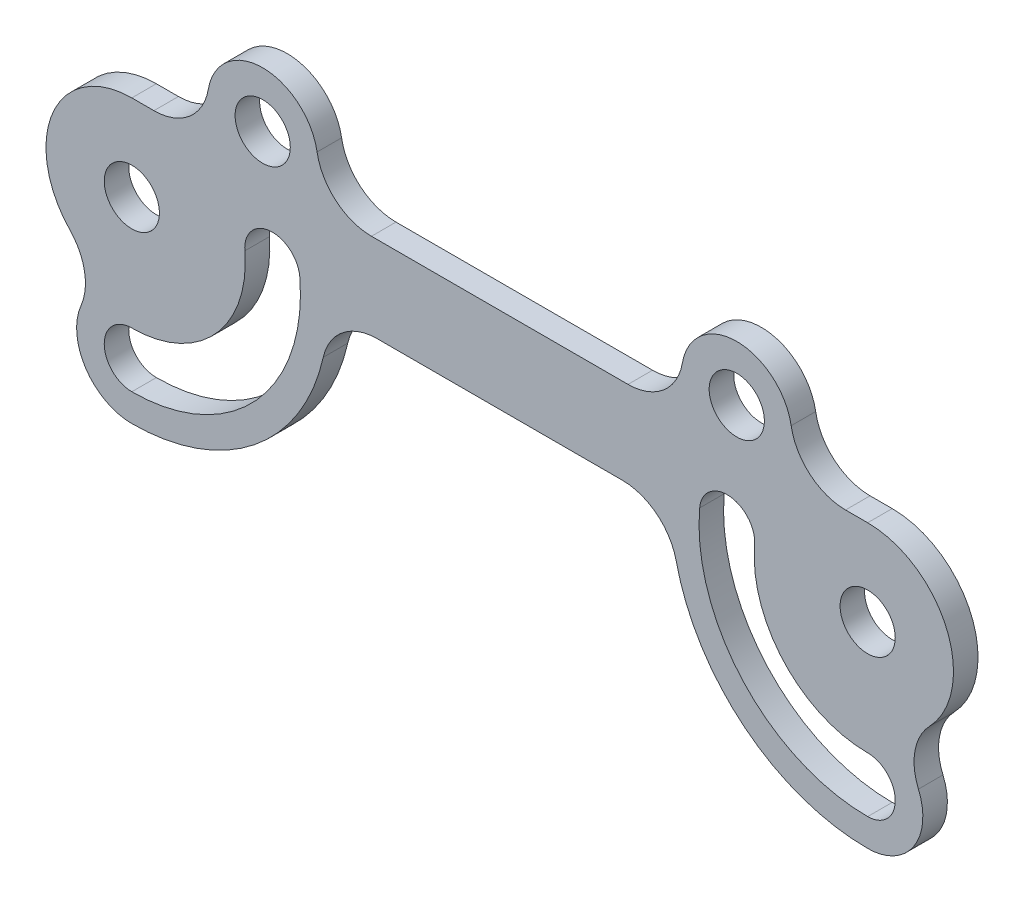
SolidWorks part; units mm, degrees
ref_plane "Front Plane" through (0, 0, 0) normal (0, 0, 1) x (1, 0, 0)
ref_plane "Top Plane" through (0, 0, 0) normal (0, 1, 0) x (1, 0, 0)
ref_plane "Right Plane" through (0, 0, 0) normal (1, 0, 0) x (0, 0, -1)
sketch "Sketch1" plane through (0, 0, 0) normal (0, 0, 1) x (1, 0, 0)
  line L0 (5.5562, 0) -> (42.0688, 0)
  line L1 (0, 5.5562) -> (47.625, 5.5562)
  line L2 (0, 5.5562) -> (0, -5.5562) construction
  line L3 (0, -5.5562) -> (47.625, -5.5562) construction
  line L4 (47.625, 5.5562) -> (47.625, -5.5562) construction
  line L5 (0, 5.5562) -> (47.625, 5.5562) construction
  line L10 (47.625, 9.1281) -> (47.625, 0) construction
  line L11 (47.625, 0) -> (38.5316, 0.7956) construction
  line L12 (0, 0) -> (9.0934, 0.7956) construction
  line L13 (9.0934, 0.7956) -> (8.4708, 7.9121) construction
  line L14 (38.5316, 0.7956) -> (39.1542, 7.9121) construction
  circle A0 centre (0, 0) radius 5.5562 construction
  circle A1 centre (47.625, 0) radius 5.5562 construction
  arc A2 (0, 5.5562) -> (0, -5.5562) centre (0, 0) ccw
  arc A3 (47.625, -5.5562) -> (47.625, 5.5562) centre (47.625, 0) ccw
  circle A4 centre (0, 0) radius 1.7859
  circle A5 centre (47.625, 0) radius 1.7859
  arc A6 (0, -5.5562) -> (5.5562, 0) centre (0, 0) ccw
  arc A7 (42.0688, 0) -> (47.625, -5.5562) centre (47.625, 0) ccw
  circle A23 centre (47.625, 0) radius 9.1281 construction
  circle A25 centre (0, 0) radius 9.1281 construction
  circle A42 centre (47.625, -9.1281) radius 3.5719
  circle A43 centre (0, -9.1281) radius 3.5719
  circle A45 centre (0, -9.1281) radius 1.7859
  circle A46 centre (8.4708, 7.9121) radius 1.7859
  circle A47 centre (8.4708, 7.9121) radius 3.5719
  circle A48 centre (9.0934, 0.7956) radius 1.7859
  circle A49 centre (9.0934, 0.7956) radius 3.5719
  circle A50 centre (38.5316, 0.7956) radius 1.7859
  circle A51 centre (38.5316, 0.7956) radius 3.5719
  circle A52 centre (39.1542, 7.9121) radius 1.7859
  circle A53 centre (39.1542, 7.9121) radius 3.5719
  circle A54 centre (47.625, -9.1281) radius 1.7859
  arc A55 (7.3142, 0.6399) -> (0, -7.3422) centre (0, 0) cw
  arc A56 (0, -12.7) -> (12.6517, 1.1069) centre (0, 0) ccw
  arc A57 (0, -10.9141) -> (10.8725, 0.9512) centre (0, 0) ccw
  arc A58 (40.3108, 0.6399) -> (47.625, -7.3422) centre (47.625, 0) ccw
  arc A59 (36.7525, 0.9512) -> (47.625, -10.9141) centre (47.625, 0) ccw
  arc A60 (34.9733, 1.1069) -> (47.625, -12.7) centre (47.625, 0) ccw
  point P46 (48.9706, -12.4368)
  point P47 (0, 0)
  point P48 (0, 0)
  dimension "D1" = 7.1437
  dimension "D2" = 11.1125
  dimension "D3" = 3.5719
  dimension "D5" = 95
  dimension "D6" = 95
  dimension "D4" = 47.625
extrude "Boss-Extrude1" add sketch "Sketch1" along normal blind 1.5875 contours A49 A47 L1 A2 A6 L0 A4 | A60 A51 A53 L1 A47 A49 A56 L0 | A53 A51 L0 A7 A3 L1 A5 | L1 A47 A46 | L1 A53 A52 | L1 A47 | A57 L0 A49 A55 A48 | L1 A53 | A59 A50 A58 L0 A51 | L0 A60 A42 A59 A51 | A51 A58 A42 A7 L0 | A59 A42 A58 A54 | A59 L0 A51 | L0 A58 A51 | A57 A43 A56 L0 A49 | A55 A49 L0 A6 A43 | A55 L0 A49 | A57 A49 L0 | A57 A45 A55 A43 | A51 A60 L0 | L0 A56 A49 region at (3.8006, -3.8006, 0) region at (4.4947, -4.1223, 0) region at (6.2738, 2.8491, 0) region at (6.6157, -0.7933, 0) region at (1.4594, -5.9772, 0) region at (8.4708, 5.062, 0) region at (23.8125, 2.8962, 0) region at (8.1808, -7.5172, 0) region at (7.2448, 11.168, 0) region at (12.6579, 0.2763, 0) region at (11.497, -0.9285, 0) region at (37.9283, 11.168, 0) region at (39.1542, 5.062, 0) region at (34.9671, 0.2763, 0) region at (39.4442, -7.5172, 0) region at (44.732, 5.3748, 0) region at (41.1033, 3.1521, 0) region at (36.128, -0.9285, 0) region at (45.6504, -11.9845, 0) region at (43.1303, -4.1223, 0) region at (41.0093, -0.7933, 0)
fillet "Fillet1" radius 3.5719 8 edges at (47.625, -5.5562, 0.7937) (41.839, 5.5562, 0.7937) (34.925, 0, 0.7937) (36.4694, 5.5562, 0.7937) (12.7, 0, 0.7937) (0, -5.5562, 0.7937) (11.1556, 5.5562, 0.7937) (5.786, 5.5562, 0.7937)
